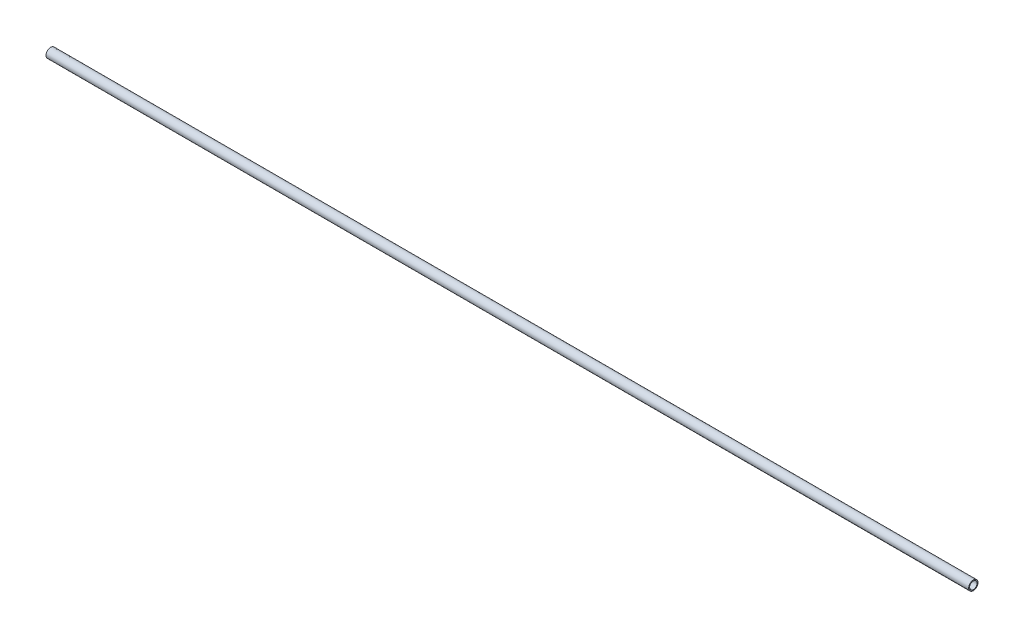
SolidWorks part; units mm, degrees
ref_plane "Front Plane" through (0, 0, 0) normal (0, 0, 1) x (1, 0, 0)
ref_plane "Top Plane" through (0, 0, 0) normal (0, 1, 0) x (1, 0, 0)
ref_plane "Right Plane" through (0, 0, 0) normal (1, 0, 0) x (0, 0, -1)
ref_axis "Axis1" through (-88.99, 0, 0) along (1, 0, 0)
sketch "Sketch1" plane through (0, 0, 0) normal (1, 0, 0) x (0, 0, -1)
  circle A0 centre (0, 0) radius 0.2032
  circle A1 centre (0, 0) radius 0.254
  dimension "D1" = 0.4064
  dimension "D2" = 0.508
extrude "Boss-Extrude1" add sketch "Sketch1" along normal blind 50
